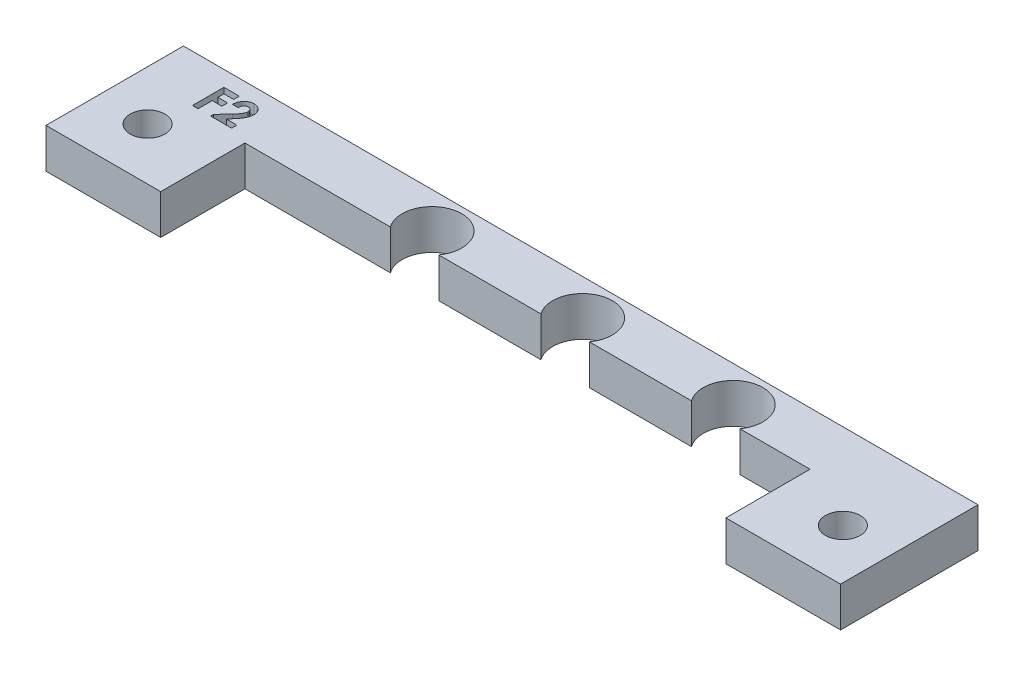
SolidWorks part; units mm, degrees
ref_plane "Front Plane" through (0, 0, 0) normal (0, 0, 1) x (1, 0, 0)
ref_plane "Top Plane" through (0, 0, 0) normal (0, 1, 0) x (1, 0, 0)
ref_plane "Right Plane" through (0, 0, 0) normal (1, 0, 0) x (0, 0, -1)
sketch "Sketch1" plane through (0, 0, 0) normal (0, 1, 0) x (1, 0, 0)
  line L0 (-9.4102, -26.3374) -> (-20.9602, -26.3374)
  line L1 (-20.9602, -26.3374) -> (-20.9602, -0.8374)
  line L2 (-20.9602, -0.8374) -> (-1.8302, -0.8374)
  line L3 (47.4898, -0.8374) -> (59.0398, -0.8374)
  line L4 (59.0398, -0.8374) -> (59.0398, -26.3374)
  line L5 (59.0398, -26.3374) -> (39.9098, -26.3374)
  line L6 (-5.6602, -25.3374) -> (36.1598, -25.3374)
  line L7 (-15.9602, -0.8374) -> (-15.9602, -26.3374) construction
  line L8 (54.0398, -26.3374) -> (54.0398, -0.8374) construction
  line L9 (1.9198, -0.8374) -> (43.7398, -0.8374)
  line L10 (-20.9602, -10.3374) -> (59.0398, -10.3374) construction
  line L11 (-15.9602, -10.3374) -> (-15.9602, -0.8374)
  line L12 (-20.9602, -18.8163) -> (59.0398, -18.8163)
  line L13 (3.0898, -18.5874) -> (3.0898, -0.8374) construction
  line L14 (3.0898, -0.8374) -> (4.9098, -0.8374) construction
  line L15 (-5.6602, -26.3374) -> (39.9098, -26.3374)
  line L16 (-20.9602, -4.9779) -> (59.0398, -4.9779)
  line L17 (-20.9602, -10.3374) -> (59.0398, -10.3374)
  line L18 (47.4898, -16.8374) -> (47.4898, -26.3374)
  circle A0 centre (-15.9602, -13.5874) radius 1.75
  circle A1 centre (54.0398, -13.5874) radius 1.75
  line B0 (-1.8302, -0.8374) -> (-1.8302, -16.8374)
  line B1 (-1.8302, -16.8374) -> (17.1698, -16.8374)
  line B2 (17.1698, -16.8374) -> (17.1698, -0.8374)
  line B3 (17.1698, -0.8374) -> (13.4198, -0.8374)
  line B4 (13.4198, -0.8374) -> (13.4198, -1.8374)
  line B5 (13.4198, -1.8374) -> (15.4198, -1.8374)
  line B6 (15.4198, -1.8374) -> (15.4198, -15.3374)
  line B7 (15.4198, -15.3374) -> (-0.0802, -15.3374)
  line B8 (-0.0802, -15.3374) -> (-0.0802, -1.8374)
  line B9 (-0.0802, -1.8374) -> (1.9198, -1.8374)
  line B10 (1.9198, -1.8374) -> (1.9198, -0.8374)
  line B11 (1.9198, -0.8374) -> (-1.8302, -0.8374)
  line B12 (-0.0802, -1.8374) -> (15.4198, -15.3374) construction
  line B13 (-0.0802, -15.3374) -> (15.4198, -1.8374) construction
  line B14 (-0.0802, -8.5874) -> (15.4198, -8.5874) construction
  line B15 (1.9198, -1.8374) -> (13.4198, -1.8374) construction
  line B16 (7.6698, -1.8374) -> (7.6698, -15.3374) construction
  circle B17 centre (7.6698, -8.5874) radius 3
  line B18 (9.5898, -26.3374) -> (9.5898, -10.3374)
  line B19 (9.5898, -10.3374) -> (-9.4102, -10.3374)
  line B20 (-9.4102, -10.3374) -> (-9.4102, -26.3374)
  line B21 (-9.4102, -26.3374) -> (-5.6602, -26.3374)
  line B22 (-5.6602, -26.3374) -> (-5.6602, -25.3374)
  line B23 (-5.6602, -25.3374) -> (-7.6602, -25.3374)
  line B24 (-7.6602, -25.3374) -> (-7.6602, -11.8374)
  line B25 (-7.6602, -11.8374) -> (7.8398, -11.8374)
  line B26 (7.8398, -11.8374) -> (7.8398, -25.3374)
  line B27 (7.8398, -25.3374) -> (5.8398, -25.3374)
  line B28 (5.8398, -25.3374) -> (5.8398, -26.3374)
  line B29 (5.8398, -26.3374) -> (9.5898, -26.3374)
  line B30 (7.8398, -25.3374) -> (-7.6602, -11.8374) construction
  line B31 (7.8398, -11.8374) -> (-7.6602, -25.3374) construction
  line B32 (7.8398, -18.5874) -> (-7.6602, -18.5874) construction
  line B33 (5.8398, -25.3374) -> (-5.6602, -25.3374) construction
  line B34 (0.0898, -25.3374) -> (0.0898, -11.8374) construction
  circle B35 centre (0.0898, -18.5874) radius 3
  line B36 (28.4898, -0.8374) -> (28.4898, -16.8374)
  line B37 (28.4898, -16.8374) -> (47.4898, -16.8374)
  line B38 (47.4898, -16.8374) -> (47.4898, -0.8374)
  line B39 (47.4898, -0.8374) -> (43.7398, -0.8374)
  line B40 (43.7398, -0.8374) -> (43.7398, -1.8374)
  line B41 (43.7398, -1.8374) -> (45.7398, -1.8374)
  line B42 (45.7398, -1.8374) -> (45.7398, -15.3374)
  line B43 (45.7398, -15.3374) -> (30.2398, -15.3374)
  line B44 (30.2398, -15.3374) -> (30.2398, -1.8374)
  line B45 (30.2398, -1.8374) -> (32.2398, -1.8374)
  line B46 (32.2398, -1.8374) -> (32.2398, -0.8374)
  line B47 (32.2398, -0.8374) -> (28.4898, -0.8374)
  line B48 (30.2398, -1.8374) -> (45.7398, -15.3374) construction
  line B49 (30.2398, -15.3374) -> (45.7398, -1.8374) construction
  line B50 (30.2398, -8.5874) -> (45.7398, -8.5874) construction
  line B51 (32.2398, -1.8374) -> (43.7398, -1.8374) construction
  line B52 (37.9898, -1.8374) -> (37.9898, -15.3374) construction
  circle B53 centre (37.9898, -8.5874) radius 3
  line B54 (13.3298, -0.8374) -> (13.3298, -16.8374)
  line B55 (13.3298, -16.8374) -> (32.3298, -16.8374)
  line B56 (32.3298, -16.8374) -> (32.3298, -0.8374)
  line B57 (32.3298, -0.8374) -> (28.5798, -0.8374)
  line B58 (28.5798, -0.8374) -> (28.5798, -1.8374)
  line B59 (28.5798, -1.8374) -> (30.5798, -1.8374)
  line B60 (30.5798, -1.8374) -> (30.5798, -15.3374)
  line B61 (30.5798, -15.3374) -> (15.0798, -15.3374)
  line B62 (15.0798, -15.3374) -> (15.0798, -1.8374)
  line B63 (15.0798, -1.8374) -> (17.0798, -1.8374)
  line B64 (17.0798, -1.8374) -> (17.0798, -0.8374)
  line B65 (17.0798, -0.8374) -> (13.3298, -0.8374)
  line B66 (15.0798, -1.8374) -> (30.5798, -15.3374) construction
  line B67 (15.0798, -15.3374) -> (30.5798, -1.8374) construction
  line B68 (15.0798, -8.5874) -> (30.5798, -8.5874) construction
  line B69 (17.0798, -1.8374) -> (28.5798, -1.8374) construction
  line B70 (22.8298, -1.8374) -> (22.8298, -15.3374) construction
  circle B71 centre (22.8298, -8.5874) radius 3
  line B72 (39.9098, -26.3374) -> (39.9098, -10.3374)
  line B73 (39.9098, -10.3374) -> (20.9098, -10.3374)
  line B74 (20.9098, -10.3374) -> (20.9098, -26.3374)
  line B75 (20.9098, -26.3374) -> (24.6598, -26.3374)
  line B76 (24.6598, -26.3374) -> (24.6598, -25.3374)
  line B77 (24.6598, -25.3374) -> (22.6598, -25.3374)
  line B78 (22.6598, -25.3374) -> (22.6598, -11.8374)
  line B79 (22.6598, -11.8374) -> (38.1598, -11.8374)
  line B80 (38.1598, -11.8374) -> (38.1598, -25.3374)
  line B81 (38.1598, -25.3374) -> (36.1598, -25.3374)
  line B82 (36.1598, -25.3374) -> (36.1598, -26.3374)
  line B83 (36.1598, -26.3374) -> (39.9098, -26.3374)
  line B84 (38.1598, -25.3374) -> (22.6598, -11.8374) construction
  line B85 (38.1598, -11.8374) -> (22.6598, -25.3374) construction
  line B86 (38.1598, -18.5874) -> (22.6598, -18.5874) construction
  line B87 (36.1598, -25.3374) -> (24.6598, -25.3374) construction
  line B88 (30.4098, -25.3374) -> (30.4098, -11.8374) construction
  circle B89 centre (30.4098, -18.5874) radius 3
  line B90 (24.7498, -26.3374) -> (24.7498, -10.3374)
  line B91 (24.7498, -10.3374) -> (5.7498, -10.3374)
  line B92 (5.7498, -10.3374) -> (5.7498, -26.3374)
  line B93 (5.7498, -26.3374) -> (9.4998, -26.3374)
  line B94 (9.4998, -26.3374) -> (9.4998, -25.3374)
  line B95 (9.4998, -25.3374) -> (7.4998, -25.3374)
  line B96 (7.4998, -25.3374) -> (7.4998, -11.8374)
  line B97 (7.4998, -11.8374) -> (22.9998, -11.8374)
  line B98 (22.9998, -11.8374) -> (22.9998, -25.3374)
  line B99 (22.9998, -25.3374) -> (20.9998, -25.3374)
  line B100 (20.9998, -25.3374) -> (20.9998, -26.3374)
  line B101 (20.9998, -26.3374) -> (24.7498, -26.3374)
  line B102 (22.9998, -25.3374) -> (7.4998, -11.8374) construction
  line B103 (22.9998, -11.8374) -> (7.4998, -25.3374) construction
  line B104 (22.9998, -18.5874) -> (7.4998, -18.5874) construction
  line B105 (20.9998, -25.3374) -> (9.4998, -25.3374) construction
  line B106 (15.2498, -25.3374) -> (15.2498, -11.8374) construction
  circle B107 centre (15.2498, -18.5874) radius 3
  dimension "D1" = 80
  dimension "D2" = 25.5
  dimension "D3" = 5
  dimension "D4" = 5
  dimension "D5" = 7.58
  dimension "D6" = 11.55
  dimension "D7" = 7.58
  dimension "D8" = 7.58
  dimension "D9" = 7.58
  dimension "D10" = 7.58
  dimension "D11" = 11.55
sketch_block_instance "Block1-1"
sketch_block "Block1" parameters "D1"=13, "D2"=15, "D3"=2, "D4"=1.75, "D5"=2, "D6"=2, "D7"=2, "D8"=2, "D9"=13.0756, "D10"=17, "D11"=17, "D12"=18.7479, "D13"=13, "D14"=2
sketch_block_instance "Block1-2"
sketch_block_instance "Block1-3"
sketch_block_instance "Block1-4"
sketch_block_instance "Block1-5"
sketch_block_instance "Block1-6"
extrude "Boss-Extrude1" add sketch "Sketch1" along normal blind 4 contours B20 L17 L1 L12 A0 | B0 L16 L11 L17 | L1 L17 L11 L16 | L17 B8 L16 B0 | B54 L16 B8 L17 B17 | L16 B54 L17 B6 | L16 B6 L17 B2 | B71 L17 B36 L16 B2 | L17 B44 L16 B36 | L17 B56 L16 B44 | B56 L17 B53 B42 L16 | L16 B42 L17 B38 | B38 L17 L4 L16 | B72 L12 L4 L17 B38 B37 A1 | B62 L17 B6 L16 | B60 L16 B44 L17 region at (-15.1852, 0, 18.673) region at (-8.8952, 0, 7.6577) region at (-18.4602, 0, 7.6577) region at (-0.9552, 0, 7.6577) region at (0.0642, 0, 7.6577) region at (14.2048, 0, 7.6577) region at (15.2498, 0, 7.6577) region at (16.2948, 0, 7.6577) region at (22.8298, 0, 5.1032) region at (29.3648, 0, 7.6577) region at (30.4098, 0, 7.6577) region at (31.4548, 0, 7.6577) region at (39.0348, 0, 5.1223) region at (47.6331, 0, 17.8269) region at (46.6148, 0, 7.6577) region at (53.2648, 0, 7.6577)
sketch "Sketch2" plane through (0, 4, 0) normal (0, 1, 0) x (1, 0, 0)
  text T0 "<b>F2</b>"
extrude "Cut-Extrude1" cut sketch "Sketch2" against normal blind 1
